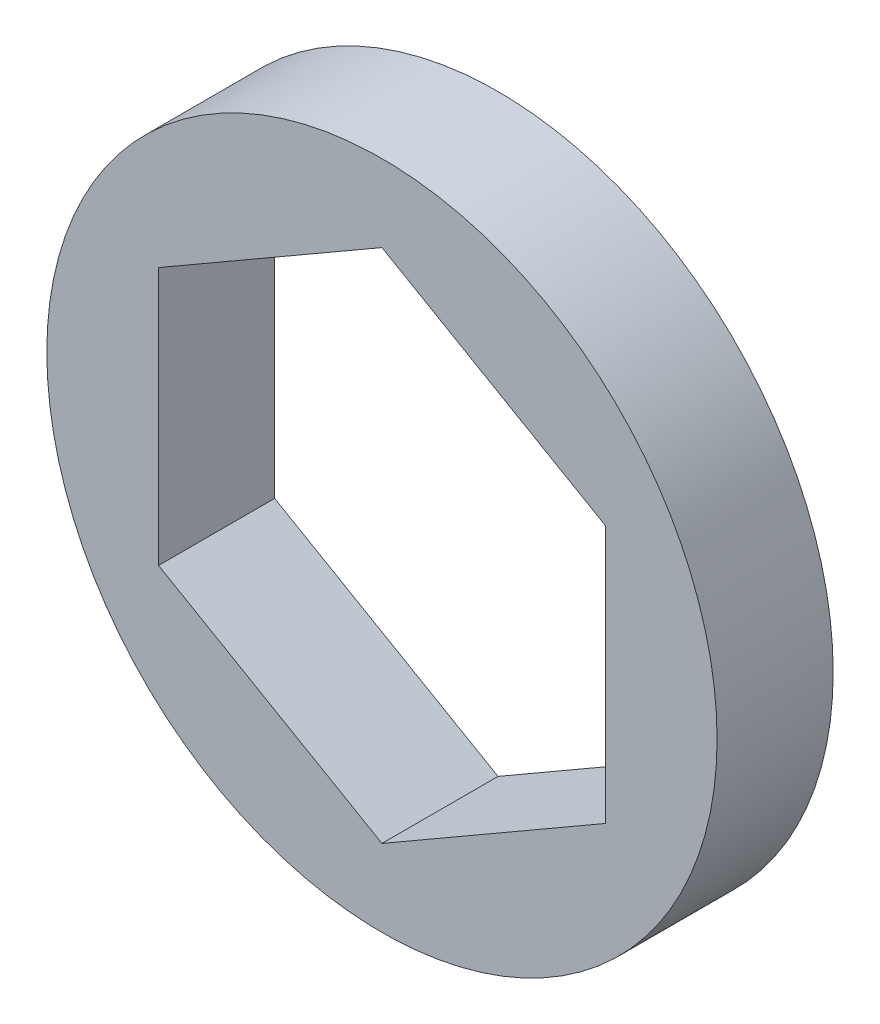
SolidWorks part; units mm, degrees
material "Nylon 101"
ref_plane "Front Plane" through (0, 0, 0) normal (0, 0, 1) x (1, 0, 0)
ref_plane "Top Plane" through (0, 0, 0) normal (0, 1, 0) x (1, 0, 0)
ref_plane "Right Plane" through (0, 0, 0) normal (1, 0, 0) x (0, 0, -1)
sketch "Sketch1" plane through (0, 0, 0) normal (0, 0, 1) x (1, 0, 0)
  line L1 (0, 7.3323) -> (-6.35, 3.6662)
  line L2 (-6.35, 3.6662) -> (-6.35, -3.6662)
  line L3 (-6.35, -3.6662) -> (0, -7.3323)
  line L4 (0, -7.3323) -> (6.35, -3.6662)
  line L5 (6.35, -3.6662) -> (6.35, 3.6662)
  line L6 (6.35, 3.6662) -> (0, 7.3323)
  circle A0 centre (0, 0) radius 6.35 construction
  circle A1 centre (0, 0) radius 9.525
  dimension "D1" = 12.7
  dimension "D2" = 19.05
extrude "Boss-Extrude1" add sketch "Sketch1" along normal blind 3.2995
